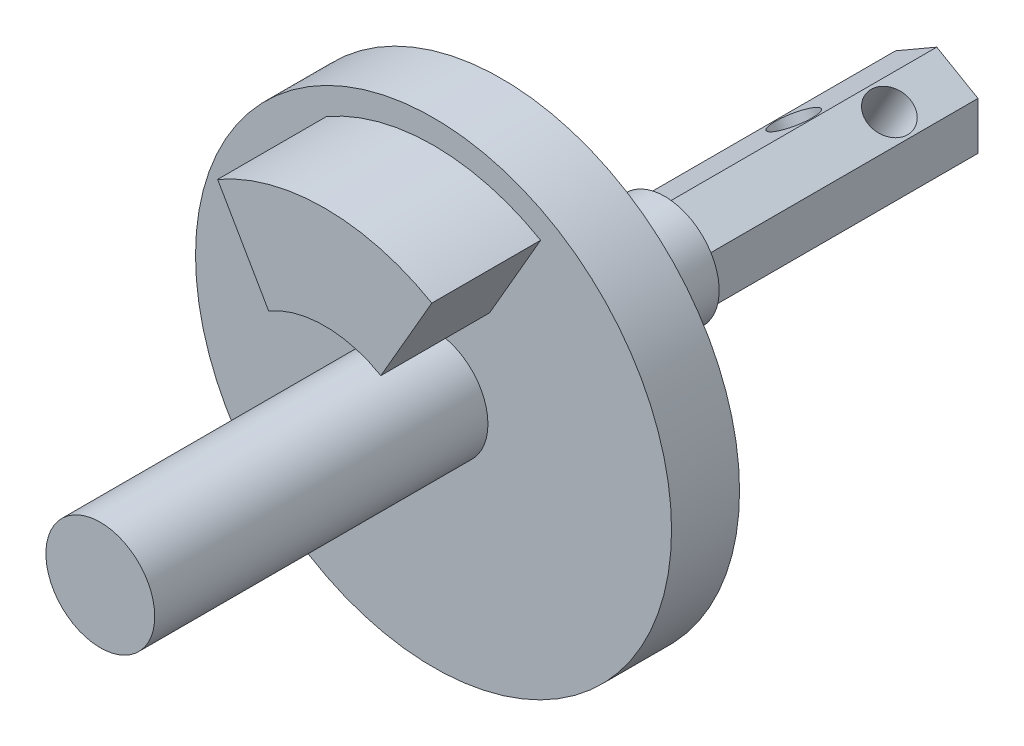
SolidWorks part; units mm, degrees
ref_plane "Front Plane" through (0, 0, 0) normal (0, 0, 1) x (1, 0, 0)
ref_plane "Top Plane" through (0, 0, 0) normal (0, 1, 0) x (1, 0, 0)
ref_plane "Right Plane" through (0, 0, 0) normal (1, 0, 0) x (0, 0, -1)
sketch "Sketch1" plane through (0, 0, 0) normal (0, 0, 1) x (1, 0, 0)
  circle A0 centre (0, 0) radius 17.5
  dimension "D1" = 35
extrude "Boss-Extrude1" add sketch "Sketch1" along normal mid plane 5
sketch "Sketch2" plane through (0, 0, 2.5) normal (0, 0, 1) x (1, 0, 0)
  line L3 (0, 0) -> (0, 11) construction
  line L4 (7.875, 13.6399) -> (4.125, 7.1447)
  line L5 (-4.125, 7.1447) -> (-7.875, 13.6399)
  arc A1 (4.125, 7.1447) -> (-4.125, 7.1447) centre (0, 0) ccw
  arc A6 (-7.875, 13.6399) -> (7.875, 13.6399) centre (0, 0) cw
  circle A7 centre (0, 0) radius 17.5 construction
  dimension "D2" = 7.5
  dimension "D3" = 1.75
  dimension "D1" = 30
extrude "Boss-Extrude2" add sketch "Sketch2" along normal blind 8
sketch "Sketch3" plane through (0, 0, 2.5) normal (0, 0, 1) x (1, 0, 0)
  circle A0 centre (0, 0) radius 4
extrude "Boss-Extrude3" add sketch "Sketch3" along normal blind 24.5
sketch "Sketch7" plane through (0, 0, -2.5) normal (0, 0, -1) x (-1, 0, 0)
  circle A0 centre (0, 0) radius 4
extrude "Boss-Extrude4" add sketch "Sketch7" along normal blind 12
sketch "Sketch9" plane through (0, 0, -14.5) normal (0, 0, -1) x (-1, 0, 0)
  line L11 (0, 3.5) -> (-3.0311, 1.75)
  line L12 (-3.0311, 1.75) -> (-3.0311, -1.75)
  line L13 (-3.0311, -1.75) -> (0, -3.5)
  line L14 (0, -3.5) -> (3.0311, -1.75)
  line L15 (3.0311, -1.75) -> (3.0311, 1.75)
  line L16 (3.0311, 1.75) -> (0, 3.5)
  point P5 (0, 0)
  point P6 (0, 0)
  point P8 (0, 0)
  point P11 (0, 0)
  point P13 (0, 0)
  point P15 (0, 0)
extrude "Boss-Extrude5" add sketch "Sketch9" along normal blind 20
sketch "Sketch10" plane through (-1.5155, -2.625, 0) normal (-0.5, -0.866, 0) x (0.866, -0.5, 0)
  line L0 (0, -34.5) -> (0, -29.5) construction
  line L1 (1.75, -34.5) -> (-1.75, -34.5) construction
  circle A0 centre (0, -29.5) radius 1.55
extrude "Cut-Extrude1" cut sketch "Sketch10" against normal blind 6.1
sketch "Sketch11" plane through (1.5155, -2.625, 0) normal (-0.5, 0.866, 0) x (0, 0, 1)
  line L0 (-34.5, 0) -> (-25.5, 0) construction
  line L3 (-34.5, -1.75) -> (-34.5, 1.75) construction
  circle A1 centre (-25.5, 0) radius 1.55
extrude "Cut-Extrude4" cut sketch "Sketch11" along normal blind 6.1
